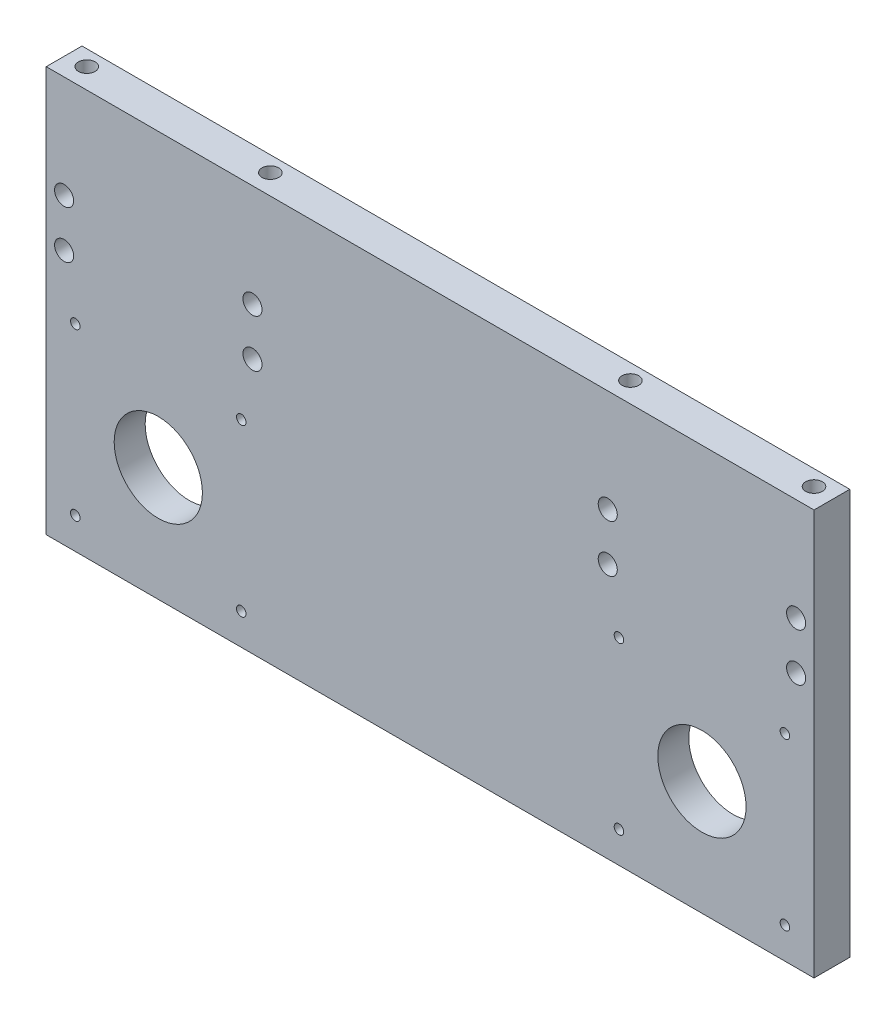
SolidWorks part; units mm, degrees
ref_plane "Płaszczyzna przednia" through (0, 0, 0) normal (0, 0, 1) x (1, 0, 0)
ref_plane "Płaszczyzna górna" through (0, 0, 0) normal (0, 1, 0) x (1, 0, 0)
ref_plane "Płaszczyzna prawa" through (0, 0, 0) normal (1, 0, 0) x (0, 0, -1)
sketch "Szkic1" plane through (0, 0, 0) normal (0, 0, 1) x (1, 0, 0)
  line L1 (161, -85) -> (-161, -85)
  line L2 (161, -85) -> (161, 85)
  line L3 (161, 85) -> (-161, 85)
  line L4 (-161, -85) -> (-161, 85)
  line L5 (161, -85) -> (-161, 85) construction
  line L6 (161, 85) -> (-161, -85) construction
  point P0 (0, 0)
  dimension "D1" = 322
  dimension "D2" = 170
extrude "Dodanie-wyciągnięcie1" add sketch "Szkic1" along normal blind 15
sketch "Szkic2" plane through (0, 0, 15) normal (0, 0, 1) x (1, 0, 0)
  line L2 (-161, -85) -> (161, -85) construction
  line L7 (-161, 85) -> (-161, -85) construction
  circle A1 centre (-148.8, -71.87) radius 2
  dimension "D1" = 13.13
  dimension "D2" = 12.2
  dimension "D5" = 4
extrude "Wytnij-wyciągnięcie2" cut sketch "Szkic2" against normal blind 17.75 contours A1 region at (-148.8, -71.87, 15)
pattern_linear "Szyk liniowy1" count 2 spacing 69.6 along (1, 0, 0) count 2 spacing 69.6 along (0, 1, 0) of "Wytnij-wyciągnięcie2"
sketch "Szkic5" plane through (0, 0, 0) normal (0, 0, -1) x (-1, 0, 0)
  line L1 (161, -85) -> (-161, -85) construction
  line L2 (161, 85) -> (161, -85) construction
  circle A1 centre (114, -37.07) radius 37.5
  dimension "D1" = 47.93
  dimension "D5" = 75
  dimension "D2" = 47
extrude "Wytnij-wyciągnięcie3" cut sketch "Szkic5" against normal blind 2 contours A1 region at (-114, -37.07, 0)
sketch "Szkic7" plane through (0, 0, 2) normal (0, 0, -1) x (-1, 0, 0)
  circle A3 centre (114, -37.07) radius 18.5
  dimension "D1" = 37
extrude "Wytnij-wyciągnięcie4" cut sketch "Szkic7" against normal blind 17.75 contours A3 region at (-114, -37.07, 2)
sketch "Szkic10" plane through (0, 0, 15) normal (0, 0, 1) x (1, 0, 0)
  line L0 (161, 85) -> (-161, 85) construction
  line L1 (-161, 85) -> (-161, -85) construction
  circle A0 centre (-153.5, 42) radius 4
  circle A1 centre (-153.5, 22) radius 4
  dimension "D1" = 63
  dimension "D3" = 8
  dimension "D4" = 8
  dimension "D2" = 20
  dimension "D5" = 7.5
extrude "Wytnij-wyciągnięcie7" cut sketch "Szkic10" against normal through all
pattern_linear "Szyk liniowy3" count 2 spacing 79 along (1, 0, 0) of "Wytnij-wyciągnięcie7"
pattern_linear "Szyk liniowy2" count 2 spacing 228 along (1, 0, 0) of "Wytnij-wyciągnięcie2", "Szyk liniowy1", "Wytnij-wyciągnięcie3", "Wytnij-wyciągnięcie4", "Szyk liniowy3"
sketch "Szkic8" plane through (0, 85, 0) normal (0, 1, 0) x (1, 0, 0)
  line L0 (-161, -15) -> (-161, 0) construction
  line L1 (161, -15) -> (-161, -15) construction
  line L2 (161, -15) -> (161, 0) construction
  line L3 (161, -15) -> (-161, -15) construction
  circle A0 centre (-153.8, -6.5) radius 4
  circle A1 centre (153.8, -6.5) radius 4
  dimension "D1" = 7.2
  dimension "D3" = 8
  dimension "D6" = 8
  dimension "D2" = 8.5
  dimension "D4" = 7.2
  dimension "D5" = 8.5
extrude "Wytnij-wyciągnięcie5" [suppressed] cut sketch "Szkic8" against normal blind 20
sketch "Szkic11" plane through (0, 0, 15) normal (0, 0, 1) x (1, 0, 0)
  line L0 (161, 85) -> (-161, 85) construction
  line L1 (161, -85) -> (161, 85) construction
  circle A0 centre (153.5, 32) radius 4
  circle A1 centre (153.5, 52) radius 4
  dimension "D1" = 53
  dimension "D2" = 8
  dimension "D3" = 8
  dimension "D4" = 7.5
  dimension "D5" = 20
extrude "Wytnij-wyciągnięcie8" [suppressed] cut sketch "Szkic11" against normal through all
hole_wizard "Otwór gwintowany M8x1.01" positions "Szkic12" profile "Szkic13" tap size "M8x1.0" standard "Ansi Metric"
sketch "Szkic12" plane through (0, 85, 0) normal (0, 1, 0) x (1, 0, 0)
  line L0 (-161, -6.5) -> (161, -6.5) construction
  line L1 (-161, -15) -> (-161, 0) construction
  line L2 (161, -15) -> (161, 0) construction
  line L5 (161, -15) -> (-161, -15) construction
  point P0 (-152.5, -6.5)
  point P2 (-75.5, -6.5)
  point P4 (75.5, -6.5)
  point P6 (152.5, -6.5)
  dimension "D1" = 8.5
  dimension "D2" = 8.5
  dimension "D3" = 8.5
  dimension "D4" = 77
  dimension "D5" = 77
sketch "Szkic13" plane through (-152.5, 85, 6.5) normal (1, 0, 0) x (0, 0, 1)
  line L0 (0, 0) -> (0, 23.103)
  line L1 (0, 23.103) -> (3.5, 21)
  line L2 (3.5, 21) -> (3.5, 0)
  line L5 (3.5, 0) -> (0, 0)
  line L10 (0, 23.103) -> (-3.5, 21) construction
  line L11 (0, -6.35) -> (0, 107.95) construction
  dimension "Średnica wiertła gwintu" = 7
  dimension "Głębokość otworu gwintowanego" = 21
  dimension "Kąt wiertła" = 118
cosmetic thread "Gwint otworu1" parameters "D1"=16, "D2"=8
cosmetic thread "Gwint otworu2" parameters "D1"=16, "D2"=8
cosmetic thread "Gwint otworu3" parameters "D1"=16, "D2"=8
cosmetic thread "Gwint otworu4" parameters "D1"=16, "D2"=8
